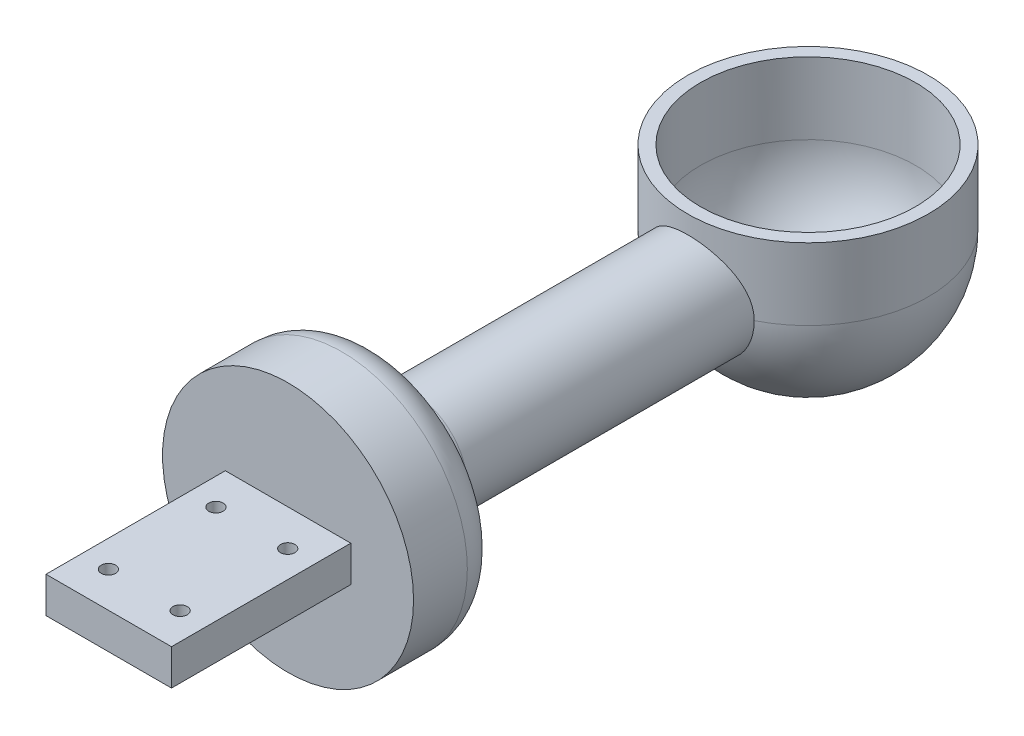
SolidWorks part; units mm, degrees
material "Custom Plastic"
ref_plane "Front Plane" through (0, 0, 0) normal (0, 0, 1) x (1, 0, 0)
ref_plane "Top Plane" through (0, 0, 0) normal (0, 1, 0) x (1, 0, 0)
ref_plane "Right Plane" through (0, 0, 0) normal (1, 0, 0) x (0, 0, -1)
sketch "Sketch1" plane through (0, 0, 0) normal (0, 0, 1) x (1, 0, 0)
  circle A0 centre (0, 0) radius 35
  dimension "D1" = 70
extrude "Boss-Extrude1" add sketch "Sketch1" along normal blind 25
sketch "Sketch2" plane through (0, 0, 0) normal (0, 0, -1) x (-1, 0, 0)
  circle A0 centre (0, 0) radius 15
  dimension "D1" = 30
extrude "Boss-Extrude2" add sketch "Sketch2" along normal blind 90
fillet "Fillet1" radius 10 2 edges at (35, 0, 0) (-15, 0, 0)
sketch "Sketch3" plane through (0, 0, 0) normal (0, 1, 0) x (1, 0, 0)
  line L0 (-35, -25) -> (35, -25) construction
  line L1 (-17.5, -75) -> (17.5, -75)
  line L2 (-17.5, -75) -> (-17.5, -25)
  line L3 (-17.5, -25) -> (17.5, -25)
  line L4 (17.5, -75) -> (17.5, -25)
  line L6 (-10, -65.1) -> (10, -65.1) construction
  line L7 (-10, -65.1) -> (-10, -35.1) construction
  line L8 (-10, -35.1) -> (10, -35.1) construction
  line L9 (10, -65.1) -> (10, -35.1) construction
  line L10 (-10, -65.1) -> (10, -35.1) construction
  line L11 (-10, -35.1) -> (10, -65.1) construction
  circle A0 centre (-10, -35.1) radius 2
  circle A1 centre (10, -35.1) radius 2
  circle A2 centre (10, -65.1) radius 2
  circle A3 centre (-10, -65.1) radius 2
  point P0 (0, -25)
  point P11 (0, -50.1)
  dimension "D3" = 4
  dimension "D1" = 35
  dimension "D2" = 50
  dimension "D4" = 30
  dimension "D5" = 20
  dimension "D6" = 10.1
extrude "Boss-Extrude3" add sketch "Sketch3" along normal mid plane 10
sketch "Sketch4" plane through (0, 0, 0) normal (0, 1, 0) x (1, 0, 0)
  line L0 (0, 90) -> (0, 150) construction
  line L1 (15, 90) -> (-15, 90) construction
  line L2 (0, 150) -> (0, 153.541)
  line L3 (0, 90) -> (0, 86.459)
  arc A0 (0, 153.541) -> (0, 86.459) centre (0, 120) ccw
  arc A1 (0, 150) -> (0, 90) centre (0, 120) ccw
  dimension "D1" = 60
revolve "Revolve1" add sketch "Sketch4" angle 180 about L0 reverse direction yes
sketch "Sketch6" plane through (0, 0, 0) normal (0, 1, 0) x (1, 0, 0)
  circle A2 centre (0, 120) radius 30
  circle A3 centre (0, 120) radius 33.541
  arc A4 (15, 90) -> (-15, 90) centre (0, 120) ccw construction
  circle A5 centre (0, 120) radius 30 construction
extrude "Boss-Extrude4" add sketch "Sketch6" along normal blind 20
